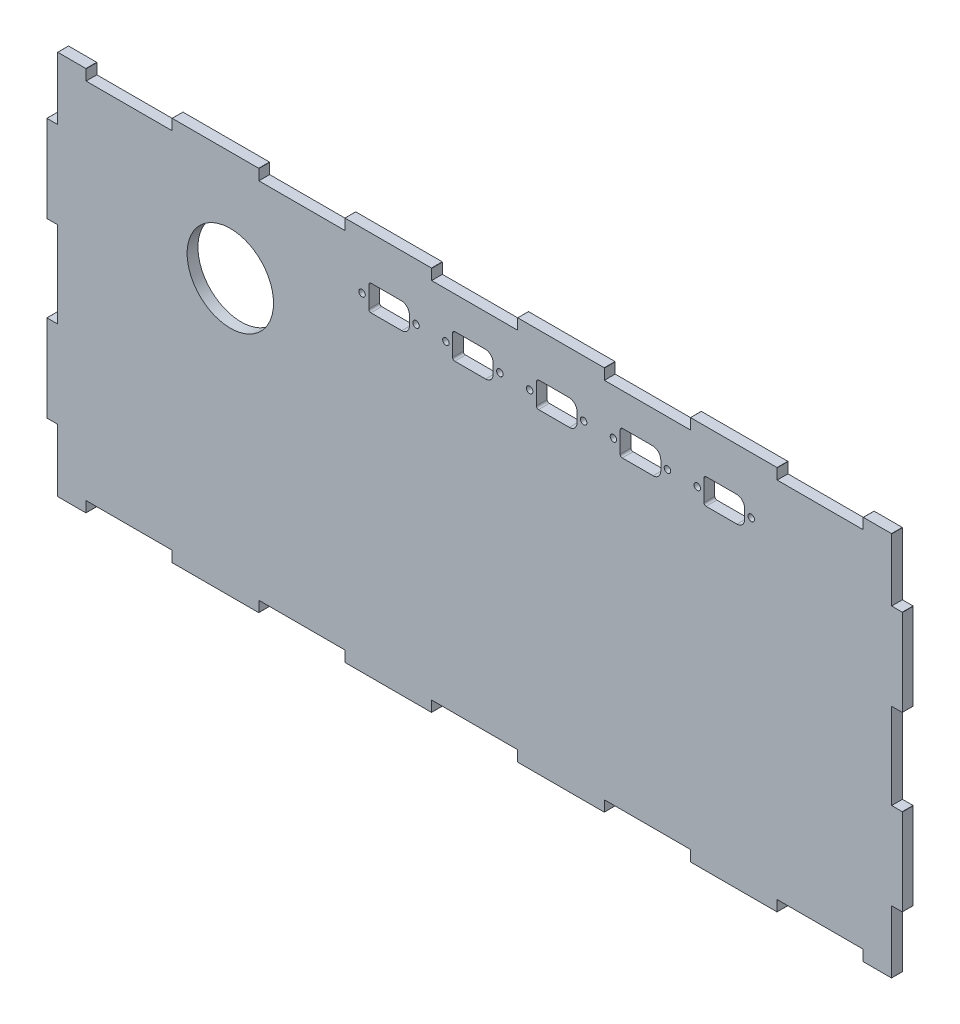
SolidWorks part; units mm, degrees
ref_plane "Front Plane" through (0, 0, 0) normal (0, 0, 1) x (1, 0, 0)
ref_plane "Top Plane" through (0, 0, 0) normal (0, 1, 0) x (1, 0, 0)
ref_plane "Right Plane" through (0, 0, 0) normal (1, 0, 0) x (0, 0, -1)
sketch "Model" plane through (0, 0, 0) normal (0, 0, 1) x (1, 0, 0)
  line L0 (-179.94, -89.08) -> (-179.93, -89.07)
  line L1 (-179.93, -89.07) -> (-179.92, -89.05)
  line L2 (-179.92, -89.05) -> (-179.91, -89.04)
  line L3 (-179.91, -89.04) -> (-179.9, -89.02)
  line L4 (-179.9, -89.02) -> (-179.9, -84.1)
  line L5 (-179.9, -84.1) -> (-140.1, -84.1)
  line L6 (-140.1, -84.1) -> (-140.1, -89.02)
  line L7 (-140.1, -89.02) -> (-140.08, -89.06)
  line L8 (-140.08, -89.06) -> (-140.07, -89.07)
  line L9 (-140.07, -89.07) -> (-140.05, -89.08)
  line L10 (-140.05, -89.08) -> (-140.04, -89.09)
  line L11 (-140.04, -89.09) -> (-140.02, -89.1)
  line L12 (-140.02, -89.1) -> (-99.98, -89.1)
  line L13 (-99.98, -89.1) -> (-99.94, -89.08)
  line L14 (-99.94, -89.08) -> (-99.93, -89.07)
  line L15 (-99.93, -89.07) -> (-99.92, -89.05)
  line L16 (-99.92, -89.05) -> (-99.91, -89.04)
  line L17 (-99.91, -89.04) -> (-99.9, -89.02)
  line L18 (-99.9, -89.02) -> (-99.9, -84.1)
  line L19 (-99.9, -84.1) -> (-60.1, -84.1)
  line L20 (-60.1, -84.1) -> (-60.1, -89.02)
  line L21 (-60.1, -89.02) -> (-60.08, -89.06)
  line L22 (-60.08, -89.06) -> (-60.07, -89.07)
  line L23 (-60.07, -89.07) -> (-60.05, -89.08)
  line L24 (-60.05, -89.08) -> (-60.04, -89.09)
  line L25 (-60.04, -89.09) -> (-60.02, -89.1)
  line L26 (-60.02, -89.1) -> (-19.98, -89.1)
  line L27 (-19.98, -89.1) -> (-19.94, -89.08)
  line L28 (-19.94, -89.08) -> (-19.93, -89.07)
  line L29 (-19.93, -89.07) -> (-19.92, -89.05)
  line L30 (-19.92, -89.05) -> (-19.91, -89.04)
  line L31 (-19.91, -89.04) -> (-19.9, -89.02)
  line L32 (-19.9, -89.02) -> (-19.9, -84.1)
  line L33 (-19.9, -84.1) -> (19.9, -84.1)
  line L34 (19.9, -84.1) -> (19.9, -89.02)
  line L35 (19.9, -89.02) -> (19.92, -89.06)
  line L36 (19.92, -89.06) -> (19.93, -89.07)
  line L37 (19.93, -89.07) -> (19.95, -89.08)
  line L38 (19.95, -89.08) -> (19.96, -89.09)
  line L39 (19.96, -89.09) -> (19.98, -89.1)
  line L40 (19.98, -89.1) -> (60.02, -89.1)
  line L41 (60.02, -89.1) -> (60.06, -89.08)
  line L42 (60.06, -89.08) -> (60.07, -89.07)
  line L43 (60.07, -89.07) -> (60.08, -89.05)
  line L44 (60.08, -89.05) -> (60.09, -89.04)
  line L45 (60.09, -89.04) -> (60.1, -89.02)
  line L46 (60.1, -89.02) -> (60.1, -84.1)
  line L47 (60.1, -84.1) -> (99.9, -84.1)
  line L48 (99.9, -84.1) -> (99.9, -89.02)
  line L49 (99.9, -89.02) -> (99.92, -89.06)
  line L50 (99.92, -89.06) -> (99.93, -89.07)
  line L51 (99.93, -89.07) -> (99.95, -89.08)
  line L52 (99.95, -89.08) -> (99.96, -89.09)
  line L53 (99.96, -89.09) -> (99.98, -89.1)
  line L54 (99.98, -89.1) -> (140.02, -89.1)
  line L55 (140.02, -89.1) -> (140.06, -89.08)
  line L56 (140.06, -89.08) -> (140.07, -89.07)
  line L57 (140.07, -89.07) -> (140.08, -89.05)
  line L58 (140.08, -89.05) -> (140.09, -89.04)
  line L59 (140.09, -89.04) -> (140.1, -89.02)
  line L60 (140.1, -89.02) -> (140.1, -84.1)
  line L61 (140.1, -84.1) -> (179.9, -84.1)
  line L62 (179.9, -84.1) -> (179.9, -89.02)
  line L63 (179.9, -89.02) -> (179.92, -89.06)
  line L64 (179.92, -89.06) -> (179.93, -89.07)
  line L65 (179.93, -89.07) -> (179.95, -89.08)
  line L66 (179.95, -89.08) -> (179.96, -89.09)
  line L67 (179.96, -89.09) -> (179.98, -89.1)
  line L68 (179.98, -89.1) -> (193.02, -89.1)
  line L69 (193.02, -89.1) -> (193.06, -89.08)
  line L70 (193.06, -89.08) -> (193.07, -89.07)
  line L71 (193.07, -89.07) -> (193.08, -89.05)
  line L72 (193.08, -89.05) -> (193.09, -89.04)
  line L73 (193.09, -89.04) -> (193.1, -89.02)
  line L74 (193.1, -89.02) -> (193.1, -60.1)
  line L75 (193.1, -60.1) -> (198.02, -60.1)
  line L76 (198.02, -60.1) -> (198.06, -60.08)
  line L77 (198.06, -60.08) -> (198.07, -60.07)
  line L78 (198.07, -60.07) -> (198.08, -60.05)
  line L79 (198.08, -60.05) -> (198.09, -60.04)
  line L80 (198.09, -60.04) -> (198.1, -60.02)
  line L81 (198.1, -60.02) -> (198.1, -19.98)
  line L82 (198.1, -19.98) -> (198.08, -19.94)
  line L83 (198.08, -19.94) -> (198.07, -19.93)
  line L84 (198.07, -19.93) -> (198.05, -19.92)
  line L85 (198.05, -19.92) -> (198.04, -19.91)
  line L86 (198.04, -19.91) -> (198.02, -19.9)
  line L87 (198.02, -19.9) -> (193.1, -19.9)
  line L88 (193.1, -19.9) -> (193.1, 19.9)
  line L89 (193.1, 19.9) -> (198.02, 19.9)
  line L90 (198.02, 19.9) -> (198.06, 19.92)
  line L91 (198.06, 19.92) -> (198.07, 19.93)
  line L92 (198.07, 19.93) -> (198.08, 19.95)
  line L93 (198.08, 19.95) -> (198.09, 19.96)
  line L94 (198.09, 19.96) -> (198.1, 19.98)
  line L95 (198.1, 19.98) -> (198.1, 60.02)
  line L96 (198.1, 60.02) -> (198.08, 60.06)
  line L97 (198.08, 60.06) -> (198.07, 60.07)
  line L98 (198.07, 60.07) -> (198.05, 60.08)
  line L99 (198.05, 60.08) -> (198.04, 60.09)
  line L100 (198.04, 60.09) -> (198.02, 60.1)
  line L101 (198.02, 60.1) -> (193.1, 60.1)
  line L102 (193.1, 60.1) -> (193.1, 89.02)
  line L103 (193.1, 89.02) -> (193.08, 89.06)
  line L104 (193.08, 89.06) -> (193.07, 89.07)
  line L105 (193.07, 89.07) -> (193.05, 89.08)
  line L106 (193.05, 89.08) -> (193.04, 89.09)
  line L107 (193.04, 89.09) -> (193.02, 89.1)
  line L108 (193.02, 89.1) -> (179.98, 89.1)
  line L109 (179.98, 89.1) -> (179.94, 89.08)
  line L110 (179.94, 89.08) -> (179.93, 89.07)
  line L111 (179.93, 89.07) -> (179.92, 89.05)
  line L112 (179.92, 89.05) -> (179.91, 89.04)
  line L113 (179.91, 89.04) -> (179.9, 89.02)
  line L114 (179.9, 89.02) -> (179.9, 84.1)
  line L115 (179.9, 84.1) -> (140.1, 84.1)
  line L116 (140.1, 84.1) -> (140.1, 89.02)
  line L117 (140.1, 89.02) -> (140.08, 89.06)
  line L118 (140.08, 89.06) -> (140.07, 89.07)
  line L119 (140.07, 89.07) -> (140.05, 89.08)
  line L120 (140.05, 89.08) -> (140.04, 89.09)
  line L121 (140.04, 89.09) -> (140.02, 89.1)
  line L122 (140.02, 89.1) -> (99.98, 89.1)
  line L123 (99.98, 89.1) -> (99.94, 89.08)
  line L124 (99.94, 89.08) -> (99.93, 89.07)
  line L125 (99.93, 89.07) -> (99.92, 89.05)
  line L126 (99.92, 89.05) -> (99.91, 89.04)
  line L127 (99.91, 89.04) -> (99.9, 89.02)
  line L128 (99.9, 89.02) -> (99.9, 84.1)
  line L129 (99.9, 84.1) -> (60.1, 84.1)
  line L130 (60.1, 84.1) -> (60.1, 89.02)
  line L131 (60.1, 89.02) -> (60.08, 89.06)
  line L132 (60.08, 89.06) -> (60.07, 89.07)
  line L133 (60.07, 89.07) -> (60.05, 89.08)
  line L134 (60.05, 89.08) -> (60.04, 89.09)
  line L135 (60.04, 89.09) -> (60.02, 89.1)
  line L136 (60.02, 89.1) -> (19.98, 89.1)
  line L137 (19.98, 89.1) -> (19.94, 89.08)
  line L138 (19.94, 89.08) -> (19.93, 89.07)
  line L139 (19.93, 89.07) -> (19.92, 89.05)
  line L140 (19.92, 89.05) -> (19.91, 89.04)
  line L141 (19.91, 89.04) -> (19.9, 89.02)
  line L142 (19.9, 89.02) -> (19.9, 84.1)
  line L143 (19.9, 84.1) -> (-19.9, 84.1)
  line L144 (-19.9, 84.1) -> (-19.9, 89.02)
  line L145 (-19.9, 89.02) -> (-19.92, 89.06)
  line L146 (-19.92, 89.06) -> (-19.93, 89.07)
  line L147 (-19.93, 89.07) -> (-19.95, 89.08)
  line L148 (-19.95, 89.08) -> (-19.96, 89.09)
  line L149 (-19.96, 89.09) -> (-19.98, 89.1)
  line L150 (-19.98, 89.1) -> (-60.02, 89.1)
  line L151 (-60.02, 89.1) -> (-60.06, 89.08)
  line L152 (-60.06, 89.08) -> (-60.07, 89.07)
  line L153 (-60.07, 89.07) -> (-60.08, 89.05)
  line L154 (-60.08, 89.05) -> (-60.09, 89.04)
  line L155 (-60.09, 89.04) -> (-60.1, 89.02)
  line L156 (-60.1, 89.02) -> (-60.1, 84.1)
  line L157 (-60.1, 84.1) -> (-99.9, 84.1)
  line L158 (-99.9, 84.1) -> (-99.9, 89.02)
  line L159 (-99.9, 89.02) -> (-99.92, 89.06)
  line L160 (-99.92, 89.06) -> (-99.93, 89.07)
  line L161 (-99.93, 89.07) -> (-99.95, 89.08)
  line L162 (-99.95, 89.08) -> (-99.96, 89.09)
  line L163 (-99.96, 89.09) -> (-99.98, 89.1)
  line L164 (-99.98, 89.1) -> (-140.02, 89.1)
  line L165 (-140.02, 89.1) -> (-140.06, 89.08)
  line L166 (-140.06, 89.08) -> (-140.07, 89.07)
  line L167 (-140.07, 89.07) -> (-140.08, 89.05)
  line L168 (-140.08, 89.05) -> (-140.09, 89.04)
  line L169 (-140.09, 89.04) -> (-140.1, 89.02)
  line L170 (-140.1, 89.02) -> (-140.1, 84.1)
  line L171 (-140.1, 84.1) -> (-179.9, 84.1)
  line L172 (-179.9, 84.1) -> (-179.9, 89.02)
  line L173 (-179.9, 89.02) -> (-179.92, 89.06)
  line L174 (-179.92, 89.06) -> (-179.93, 89.07)
  line L175 (-179.93, 89.07) -> (-179.95, 89.08)
  line L176 (-179.95, 89.08) -> (-179.96, 89.09)
  line L177 (-179.96, 89.09) -> (-179.98, 89.1)
  line L178 (-179.98, 89.1) -> (-193.02, 89.1)
  line L179 (-193.02, 89.1) -> (-193.06, 89.08)
  line L180 (-193.06, 89.08) -> (-193.07, 89.07)
  line L181 (-193.07, 89.07) -> (-193.08, 89.05)
  line L182 (-193.08, 89.05) -> (-193.09, 89.04)
  line L183 (-193.09, 89.04) -> (-193.1, 89.02)
  line L184 (-193.1, 89.02) -> (-193.1, 60.1)
  line L185 (-193.1, 60.1) -> (-198.02, 60.1)
  line L186 (-198.02, 60.1) -> (-198.06, 60.08)
  line L187 (-198.06, 60.08) -> (-198.07, 60.07)
  line L188 (-198.07, 60.07) -> (-198.08, 60.05)
  line L189 (-198.08, 60.05) -> (-198.09, 60.04)
  line L190 (-198.09, 60.04) -> (-198.1, 60.02)
  line L191 (-198.1, 60.02) -> (-198.1, 19.98)
  line L192 (-198.1, 19.98) -> (-198.08, 19.94)
  line L193 (-198.08, 19.94) -> (-198.07, 19.93)
  line L194 (-198.07, 19.93) -> (-198.05, 19.92)
  line L195 (-198.05, 19.92) -> (-198.04, 19.91)
  line L196 (-198.04, 19.91) -> (-198.02, 19.9)
  line L197 (-198.02, 19.9) -> (-193.1, 19.9)
  line L198 (-193.1, 19.9) -> (-193.1, -19.9)
  line L199 (-193.1, -19.9) -> (-198.02, -19.9)
  line L200 (-198.02, -19.9) -> (-198.06, -19.92)
  line L201 (-198.06, -19.92) -> (-198.07, -19.93)
  line L202 (-198.07, -19.93) -> (-198.08, -19.95)
  line L203 (-198.08, -19.95) -> (-198.09, -19.96)
  line L204 (-198.09, -19.96) -> (-198.1, -19.98)
  line L205 (-198.1, -19.98) -> (-198.1, -60.02)
  line L206 (-198.1, -60.02) -> (-198.08, -60.06)
  line L207 (-198.08, -60.06) -> (-198.07, -60.07)
  line L208 (-198.07, -60.07) -> (-198.05, -60.08)
  line L209 (-198.05, -60.08) -> (-198.04, -60.09)
  line L210 (-198.04, -60.09) -> (-198.02, -60.1)
  line L211 (-198.02, -60.1) -> (-193.1, -60.1)
  line L212 (-193.1, -60.1) -> (-193.1, -89.02)
  line L213 (-193.1, -89.02) -> (-193.08, -89.06)
  line L214 (-193.08, -89.06) -> (-193.07, -89.07)
  line L215 (-193.07, -89.07) -> (-193.05, -89.08)
  line L216 (-193.05, -89.08) -> (-193.04, -89.09)
  line L217 (-193.04, -89.09) -> (-193.02, -89.1)
  line L218 (-193.02, -89.1) -> (-179.98, -89.1)
  line L219 (-179.98, -89.1) -> (-179.94, -89.08)
extrude "Boss-Extrude1" add sketch "Model" along normal blind 5
sketch "Sketch2" plane through (0, 0, 5) normal (0, 0, 1) x (1, 0, 0)
  line L5 (-30.2088, 62.97) -> (-10.2088, 62.97) construction
  line L13 (-33.7338, 57.12) -> (-48.0088, 57.12)
  line L14 (-47.8088, 69.02) -> (-33.9338, 69.02)
  line L15 (-49.0088, 58.12) -> (-49.0088, 67.82)
  line L16 (-30.2088, 60.645) -> (-30.2088, 65.295)
  line L17 (5.0662, 57.12) -> (-9.2088, 57.12)
  line L18 (-9.0088, 69.02) -> (4.8662, 69.02)
  line L19 (-10.2088, 58.12) -> (-10.2088, 67.82)
  line L20 (8.5912, 60.645) -> (8.5912, 65.295)
  line L21 (43.8662, 57.12) -> (29.5912, 57.12)
  line L22 (29.7912, 69.02) -> (43.6662, 69.02)
  line L23 (28.5912, 58.12) -> (28.5912, 67.82)
  line L24 (47.3912, 60.645) -> (47.3912, 65.295)
  line L25 (82.6662, 57.12) -> (68.3912, 57.12)
  line L26 (68.5912, 69.02) -> (82.4662, 69.02)
  line L27 (67.3912, 58.12) -> (67.3912, 67.82)
  line L28 (86.1912, 60.645) -> (86.1912, 65.295)
  line L37 (8.5912, 62.97) -> (28.5912, 62.97) construction
  line L38 (47.3912, 62.97) -> (67.3912, 62.97) construction
  line L39 (121.4662, 57.12) -> (107.1912, 57.12)
  line L40 (107.3912, 69.02) -> (121.2662, 69.02)
  line L45 (106.1912, 58.12) -> (106.1912, 67.82)
  line L46 (124.9912, 60.645) -> (124.9912, 65.295)
  line L47 (86.1912, 62.97) -> (106.1912, 62.97) construction
  line L48 (-52.1088, 62.97) -> (-49.0088, 62.97) construction
  line L49 (-13.3088, 62.97) -> (-10.2088, 62.97) construction
  line L50 (25.4912, 62.97) -> (28.5912, 62.97) construction
  line L51 (64.2912, 62.97) -> (67.3912, 62.97) construction
  line L52 (103.0912, 62.97) -> (106.1912, 62.97) construction
  line L53 (128.0912, 62.97) -> (193.1, 62.97) construction
  line L54 (193.1, 60.1) -> (193.1, 89.02) construction
  line L55 (193.1, 62.97) -> (193.1, 89.02) construction
  arc A12 (-30.2088, 60.645) -> (-33.7338, 57.12) centre (-33.7338, 60.645) cw
  arc A13 (-30.2088, 65.295) -> (-33.9338, 69.02) centre (-33.9338, 65.295) ccw
  arc A14 (-48.0088, 57.12) -> (-49.0088, 58.12) centre (-48.0088, 58.12) cw
  arc A15 (-49.0088, 67.82) -> (-47.8088, 69.02) centre (-47.8088, 67.82) cw
  arc A16 (8.5912, 60.645) -> (5.0662, 57.12) centre (5.0662, 60.645) cw
  arc A17 (8.5912, 65.295) -> (4.8662, 69.02) centre (4.8662, 65.295) ccw
  arc A18 (-9.2088, 57.12) -> (-10.2088, 58.12) centre (-9.2088, 58.12) cw
  arc A19 (-10.2088, 67.82) -> (-9.0088, 69.02) centre (-9.0088, 67.82) cw
  arc A20 (47.3912, 60.645) -> (43.8662, 57.12) centre (43.8662, 60.645) cw
  arc A21 (47.3912, 65.295) -> (43.6662, 69.02) centre (43.6662, 65.295) ccw
  arc A22 (29.5912, 57.12) -> (28.5912, 58.12) centre (29.5912, 58.12) cw
  arc A23 (28.5912, 67.82) -> (29.7912, 69.02) centre (29.7912, 67.82) cw
  arc A24 (86.1912, 60.645) -> (82.6662, 57.12) centre (82.6662, 60.645) cw
  arc A25 (86.1912, 65.295) -> (82.4662, 69.02) centre (82.4662, 65.295) ccw
  arc A26 (68.3912, 57.12) -> (67.3912, 58.12) centre (68.3912, 58.12) cw
  arc A27 (67.3912, 67.82) -> (68.5912, 69.02) centre (68.5912, 67.82) cw
  arc A40 (124.9912, 60.645) -> (121.4662, 57.12) centre (121.4662, 60.645) cw
  arc A41 (124.9912, 65.295) -> (121.2662, 69.02) centre (121.2662, 65.295) ccw
  arc A42 (107.1912, 57.12) -> (106.1912, 58.12) centre (107.1912, 58.12) cw
  arc A43 (106.1912, 67.82) -> (107.3912, 69.02) centre (107.3912, 67.82) cw
  circle A44 centre (-52.1088, 62.97) radius 1.5
  circle A45 centre (-27.1088, 62.97) radius 1.5
  circle A46 centre (-13.3088, 62.97) radius 1.5
  circle A47 centre (11.6912, 62.97) radius 1.5
  circle A48 centre (25.4912, 62.97) radius 1.5
  circle A49 centre (50.4912, 62.97) radius 1.5
  circle A50 centre (64.2912, 62.97) radius 1.5
  circle A51 centre (89.2912, 62.97) radius 1.5
  circle A52 centre (103.0912, 62.97) radius 1.5
  circle A53 centre (128.0912, 62.97) radius 1.5
  dimension "D7" = 3
  dimension "D9" = 3
  dimension "D1" = 20
  dimension "D2" = 20
  dimension "D3" = 20
  dimension "D4" = 20
  dimension "D5" = 25
extrude "Cut-Extrude1" cut sketch "Sketch2" against normal through all
sketch "Sketch3" plane through (0, 0, 5) normal (0, 0, 1) x (1, 0, 0)
  line L0 (-113.1, 38.4) -> (-113.1, 89.1) construction
  line L2 (-198.1, 38.4) -> (-113.1, 38.4) construction
  line L3 (-198.1, 60.02) -> (-198.1, 19.98) construction
  line L4 (-99.98, 89.1) -> (-140.02, 89.1) construction
  circle A0 centre (-113.1, 38.4) radius 20
  dimension "D1" = 40
  dimension "D2" = 85
  dimension "D3" = 50.7
extrude "Cut-Extrude2" cut sketch "Sketch3" against normal through all
